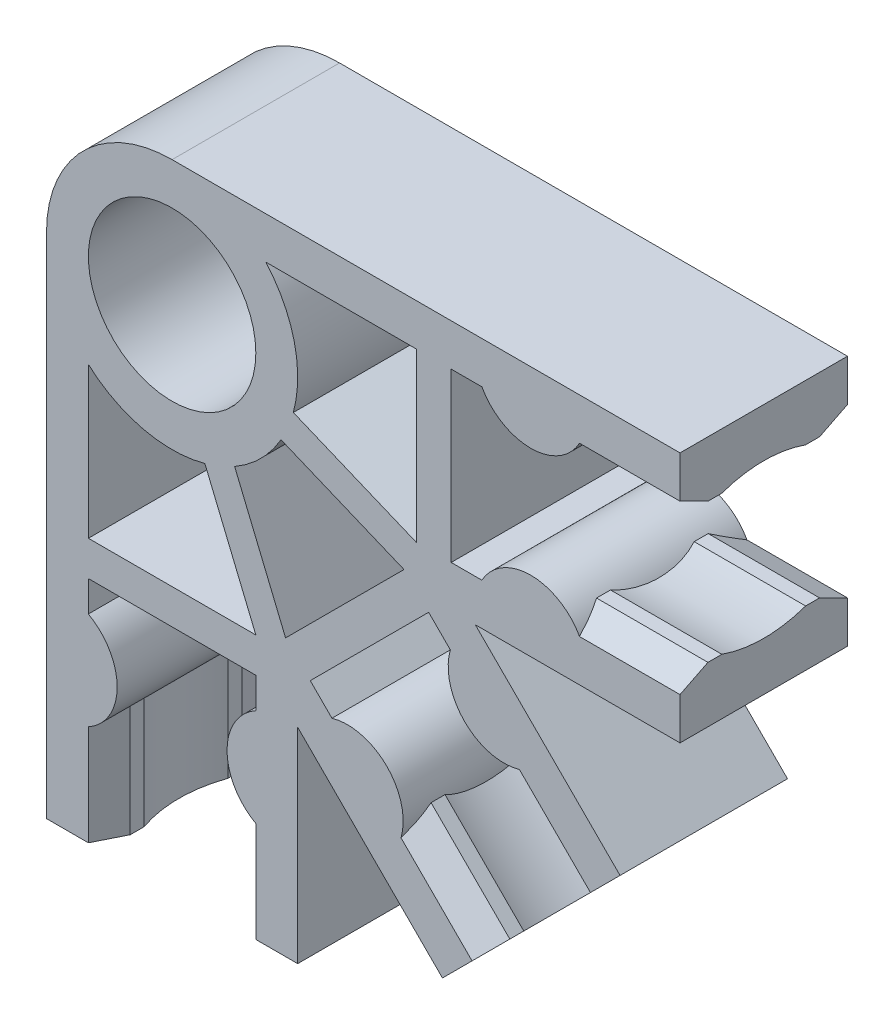
SolidWorks part; units mm, degrees
ref_plane "前视基准面" through (0, 0, 0) normal (0, 0, 1) x (1, 0, 0)
ref_plane "上视基准面" through (0, 0, 0) normal (0, 1, 0) x (1, 0, 0)
ref_plane "右视基准面" through (0, 0, 0) normal (1, 0, 0) x (0, 0, -1)
sketch "草图1" plane through (0, 0, 0) normal (0, 0, 1) x (1, 0, 0)
  line L0 (-4.5, 0) -> (-4.5, -18.2)
  line L1 (4.5, 0) -> (4.5, -18.2)
  line L2 (-4.5, -18.2) -> (-3, -18.2)
  line L3 (-3, -18.2) -> (-3, -14.6)
  line L4 (4.5, -18.2) -> (3, -18.2)
  line L5 (3, -18.2) -> (3, -14.6)
  line L6 (-3, -11.1) -> (-3, -10)
  line L7 (-3, -10) -> (3, -10)
  line L8 (3, -10) -> (3, -11.1)
  arc A0 (4.5, 0) -> (-4.5, 0) centre (0, 0) ccw
  arc A1 (-3, -11.1) -> (-3, -14.6) centre (-3.9682, -12.85) cw
  arc A2 (3, -11.1) -> (3, -14.6) centre (3.9682, -12.85) ccw
  point P1 (0, 4.5)
  dimension "D1" = 9
  dimension "D10" = 14.5
  dimension "D11" = 2
  dimension "D12" = 2
  dimension "D2" = 18.2
  dimension "D3" = 18.2
  dimension "D4" = 1.5
  dimension "D5" = 1.5
  dimension "D6" = 1.1
  dimension "D7" = 1.1
  dimension "D8" = 3.5
  dimension "D9" = 3.5
extrude "凸台-拉伸1" add sketch "草图1" along normal blind 6
sketch "草图3" plane through (0, -18.2, 0) normal (0, -1, 0) x (1, 0, 0)
  line L0 (-3, 6) -> (-3, 0)
  line L1 (-3, 0) -> (-2.5, 1)
  line L2 (-2.5, 1) -> (-2.5, 1.5)
  line L3 (-3, 6) -> (-2.5, 5)
  line L4 (-2.5, 5) -> (-2.5, 4.5)
  line L5 (0, 0) -> (0, 6.4845) construction
  line L6 (3, 0) -> (2.5, 1)
  line L7 (2.5, 1) -> (2.5, 1.5)
  line L8 (2.5, 5) -> (2.5, 4.5)
  line L9 (3, 6) -> (2.5, 5)
  line L10 (3, 6) -> (3, 0)
  arc A0 (-2.5, 1.5) -> (-2.5, 4.5) centre (1.7426, 3) cw
  arc A1 (2.5, 1.5) -> (2.5, 4.5) centre (-1.7426, 3) ccw
  dimension "D7" = 4.5
  dimension "D1" = 0.5
  dimension "D2" = 0.5
  dimension "D3" = 0.5
  dimension "D4" = 0.5
  dimension "D5" = 1.5
  dimension "D6" = 1.5
extrude "凸台-拉伸2" add sketch "草图3" against normal up to next
ref_axis "Axis" through (0, 0, 0) along (0, 0, 1)
pattern_circular "阵列(圆周)1" count 3 every 45 about axis through (0, 0, 0) along (0, 0, 1) of "凸台-拉伸1", "凸台-拉伸2"
sketch "草图4" plane through (0, 0, 6) normal (0, 0, 1) x (1, 0, 0)
  line L0 (8.75, 3) -> (3.3541, 3)
  line L1 (8.75, -3) -> (8.75, 3)
  line L2 (8.75, -3) -> (4.3439, -1.1749)
  line L3 (10, -3) -> (10, 3) construction
  line L4 (0, 0) -> (10.864, -4.5) construction
  line L5 (0, 0) -> (7.0711, -7.0711) construction
  line L6 (4.9497, -9.1924) -> (9.1924, -4.9497) construction
  line L7 (0, 0) -> (4.5, -10.864) construction
  line L8 (3, -8.75) -> (1.1749, -4.3439)
  line L9 (3, -8.75) -> (-3, -8.75)
  line L10 (-3, -8.75) -> (-3, -3.3541)
  line L11 (8.3085, -4.0659) -> (4.0659, -8.3085)
  line L12 (8.3085, -4.0659) -> (3.9024, -2.2408)
  line L13 (4.0659, -8.3085) -> (2.2408, -3.9024)
  circle A0 centre (0, 0) radius 3
  arc A1 (-3, -3.3541) -> (1.1749, -4.3439) centre (0, 0) ccw
  arc A2 (2.2408, -3.9024) -> (3.9024, -2.2408) centre (0, 0) ccw
  arc A3 (4.3439, -1.1749) -> (3.3541, 3) centre (0, 0) ccw
  point P24 (6.1872, -6.1872)
  dimension "D1" = 6
  dimension "D2" = 9
  dimension "D3" = 1.25
  dimension "D4" = 6
  dimension "D5" = 6
  dimension "D6" = 1.25
extrude "切除-拉伸1" cut sketch "草图4" against normal through all
